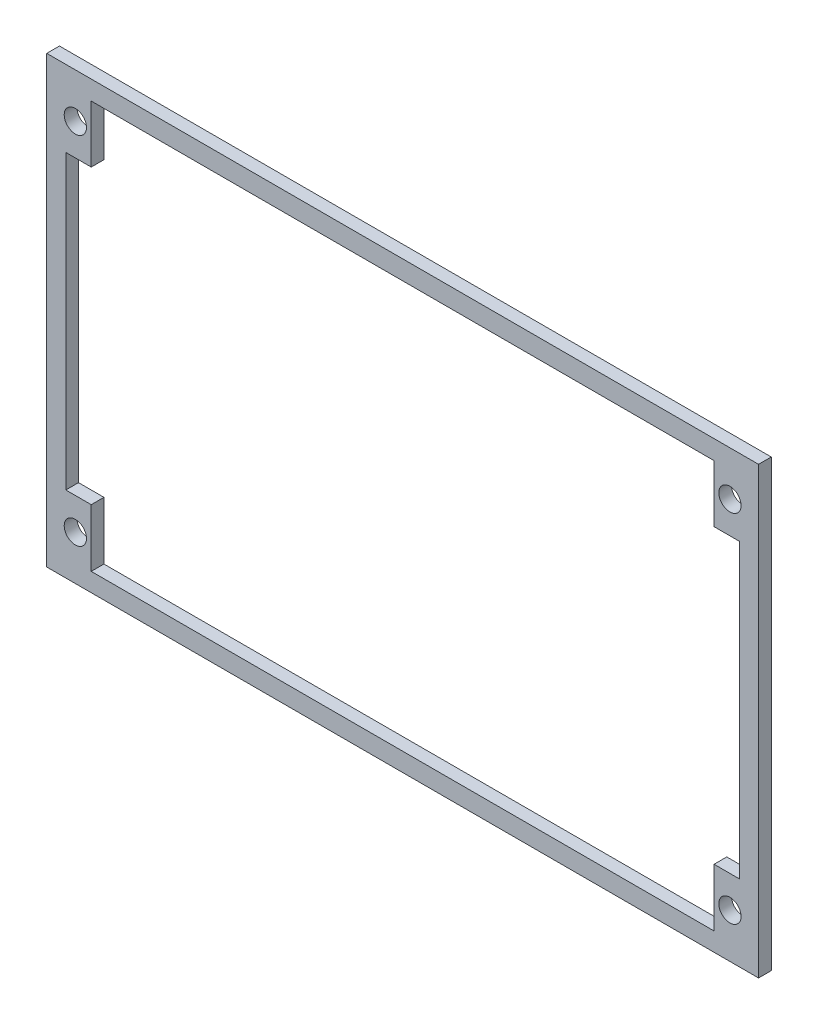
SolidWorks part; units mm, degrees
ref_plane "Ön Düzlem" through (0, 0, 0) normal (0, 0, 1) x (1, 0, 0)
ref_plane "Üst Düzlem" through (0, 0, 0) normal (0, 1, 0) x (1, 0, 0)
ref_plane "Sağ Düzlem" through (0, 0, 0) normal (1, 0, 0) x (0, 0, -1)
sketch "Sketch1" plane through (0, 0, 0) normal (0, 0, 1) x (1, 0, 0)
  line L1 (0, 0) -> (112, 0)
  line L2 (0, 0) -> (0, 70)
  line L3 (0, 70) -> (112, 70)
  line L4 (112, 0) -> (112, 70)
extrude "Boss-Extrude1" add sketch "Sketch1" along normal blind 2
sketch "Sketch2" plane through (0, 0, 2) normal (0, 0, 1) x (1, 0, 0)
  line L0 (0, 70) -> (0, 0) construction
  line L1 (7, 2.9087) -> (105, 2.9087)
  line L2 (7, 2.9087) -> (7, 67)
  line L3 (7, 67) -> (105, 67)
  line L4 (105, 2.9087) -> (105, 67)
  line L5 (112, 70) -> (0, 70) construction
  dimension "D1" = 7
  dimension "D2" = 3
extrude "Cut-Extrude1" cut sketch "Sketch2" against normal through all
sketch "Sketch3" plane through (0, 0, 2) normal (0, 0, 1) x (1, 0, 0)
  line L0 (7, 67) -> (7, 2.9087) construction
  line L1 (3, 12) -> (7, 12)
  line L2 (3, 12) -> (3, 58)
  line L3 (3, 58) -> (7, 58)
  line L4 (7, 12) -> (7, 58)
  line L5 (112, 70) -> (0, 70) construction
  line L6 (0, 70) -> (0, 0) construction
  line L7 (105, 2.9087) -> (105, 67) construction
  line L8 (105, 58) -> (109, 58)
  line L9 (105, 58) -> (105, 12)
  line L10 (105, 12) -> (109, 12)
  line L11 (109, 58) -> (109, 12)
  dimension "D1" = 12
  dimension "D2" = 3
  dimension "D3" = 4
  dimension "D4" = 12
extrude "Cut-Extrude2" cut sketch "Sketch3" against normal through all
sketch "Sketch4" plane through (0, 0, 2) normal (0, 0, 1) x (1, 0, 0)
  line L0 (0, 70) -> (0, 0) construction
  line L1 (112, 70) -> (0, 70) construction
  line L2 (0, 0) -> (112, 0) construction
  line L3 (112, 0) -> (112, 70) construction
  circle A0 centre (4.5, 63) radius 1.75
  circle A1 centre (4.5, 7) radius 1.75
  circle A2 centre (107.5, 7) radius 1.75
  circle A3 centre (107.5, 63) radius 1.75
  dimension "D1" = 4.5
  dimension "D3" = 7
  dimension "D4" = 4.5
  dimension "D2" = 7
extrude "Cut-Extrude3" cut sketch "Sketch4" against normal through all
